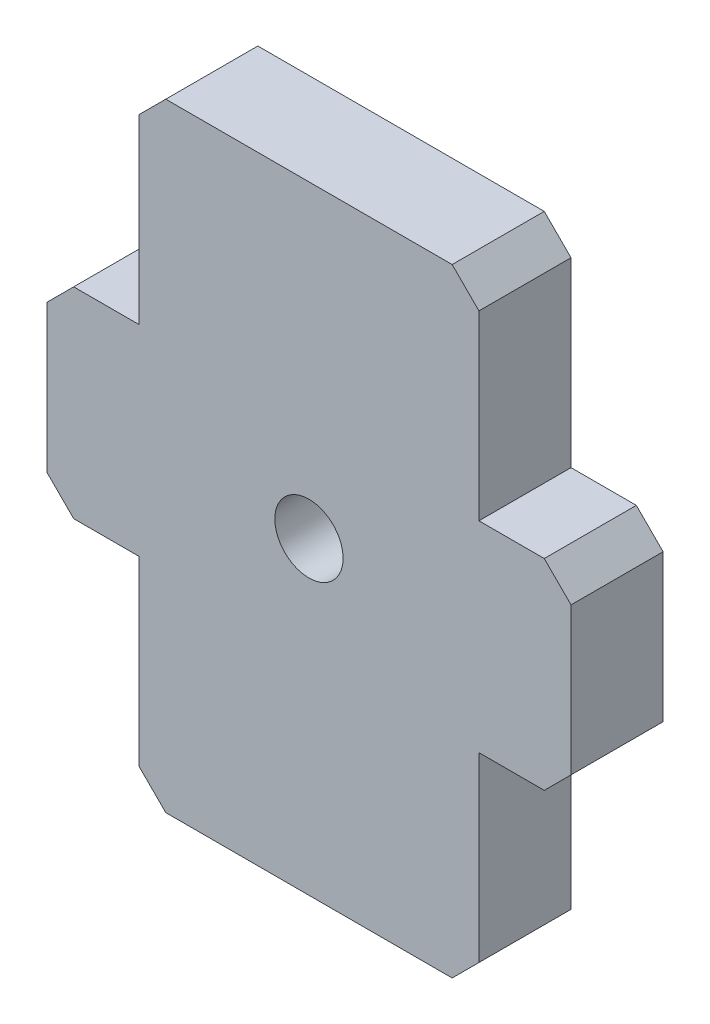
SolidWorks part; units mm, degrees
ref_plane "Front Plane" through (0, 0, 0) normal (0, 0, 1) x (1, 0, 0)
ref_plane "Top Plane" through (0, 0, 0) normal (0, 1, 0) x (1, 0, 0)
ref_plane "Right Plane" through (0, 0, 0) normal (1, 0, 0) x (0, 0, -1)
sketch "Sketch1" plane through (0, 0, 0) normal (0, 0, 1) x (1, 0, 0)
  line L1 (12.7, -23.082) -> (-12.7, -23.082)
  line L2 (12.7, -23.082) -> (12.7, 23.082)
  line L3 (12.7, 23.082) -> (-12.7, 23.082)
  line L4 (-12.7, -23.082) -> (-12.7, 23.082)
  line L5 (12.7, -23.082) -> (-12.7, 23.082) construction
  line L6 (12.7, 23.082) -> (-12.7, -23.082) construction
  point P0 (0, 0)
  dimension "D1" = 46.164
  dimension "D2" = 25.4
extrude "Boss-Extrude1" add sketch "Sketch1" against normal blind 6.88
sketch "Sketch2" plane through (0, 0, 0) normal (0, 0, 1) x (1, 0, 0)
  line L0 (-12.7, 23.082) -> (-12.7, -23.082) construction
  line L1 (-5.82, -7.5) -> (-19.58, -7.5)
  line L2 (-5.82, -7.5) -> (-5.82, 7.5)
  line L3 (-5.82, 7.5) -> (-19.58, 7.5)
  line L4 (-19.58, -7.5) -> (-19.58, 7.5)
  line L5 (-5.82, -7.5) -> (-19.58, 7.5) construction
  line L6 (-5.82, 7.5) -> (-19.58, -7.5) construction
  point P0 (-12.7, 0)
  dimension "D1" = 6.88
  dimension "D2" = 15
extrude "Boss-Extrude2" add sketch "Sketch2" against normal up to vertex (6.88 mm away) up to point (-12.7, -23.082, -6.88)
mirror "Mirror2" about plane through (0, 0, 0) normal (1, 0, 0) of "Boss-Extrude2"
sketch "Sketch3" plane through (0, 0, 0) normal (0, 0, 1) x (1, 0, 0)
  circle A0 centre (0, 0) radius 2.55
  dimension "D1" = 5.1
extrude "Cut-Extrude1" cut sketch "Sketch3" against normal through all
chamfer "Chamfer1" distance 2 angle 45 8 edges at (-12.7, 23.082, -3.44) (-19.58, 7.5, -3.44) (-19.58, -7.5, -3.44) (-12.7, -23.082, -3.44) (12.7, -23.082, -3.44) (19.58, -7.5, -3.44) (12.7, 23.082, -3.44) (19.58, 7.5, -3.44)
